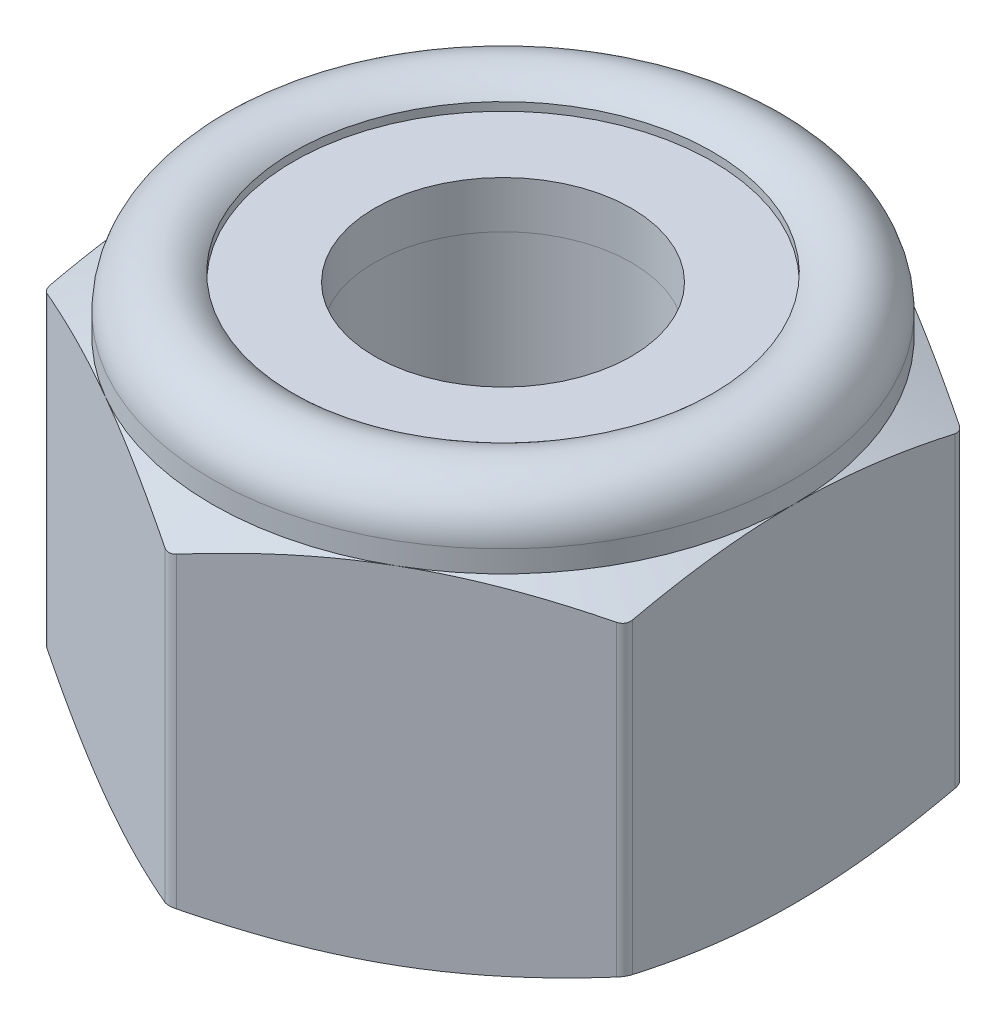
SolidWorks part; units mm, degrees
material "Alloy Steel"
ref_plane "Front Plane" through (0, 0, 0) normal (0, 0, 1) x (1, 0, 0)
ref_plane "Top Plane" through (0, 0, 0) normal (0, 1, 0) x (1, 0, 0)
ref_plane "Right Plane" through (0, 0, 0) normal (1, 0, 0) x (0, 0, -1)
sketch "Sketch1" plane through (0, 0, 0) normal (0, 0, 1) x (1, 0, 0)
  line L0 (0, -2.5) -> (0, 2.5) construction
  line L1 (3.5, 0) -> (-3.5, 0) construction
  line L2 (2, -2.5) -> (-2, -2.5) construction
  line L3 (2, -2.5) -> (2, -1.8) construction
  point P4 (0, 0)
  point P8 (0, 0)
  point P11 (0, -2.5)
  dimension "Height" = 5
  dimension "Width" = 7
  dimension "Thread Size" = 4
  dimension "Thread Pitch" = 0.7
sketch "Sketch2" plane through (0, 0, 0) normal (0, 1, 0) x (1, 0, 0)
  line L0 (-2, 0.3063) -> (-2, -0.3063) construction
  line L1 (0, 4.0415) -> (-3.5, 2.0207)
  line L2 (-3.5, 2.0207) -> (-3.5, -2.0207)
  line L3 (-3.5, -2.0207) -> (0, -4.0415)
  line L4 (0, -4.0415) -> (3.5, -2.0207)
  line L5 (3.5, -2.0207) -> (3.5, 2.0207)
  line L6 (3.5, 2.0207) -> (0, 4.0415)
  line L7 (-2, -0.3063) -> (-1.5453, -0.0438) construction
  line L8 (-1.5453, -0.0438) -> (-1.5453, 0.0437) construction
  line L9 (-1.5453, 0.0437) -> (-2, 0.3063) construction
  line L10 (-1.5453, 0) -> (-2, 0) construction
  line L11 (-1.7727, 0.175) -> (-1.7727, -0.175) construction
  line L12 (2, 0) -> (-2, 0) construction
  line L13 (3.5, 0) -> (-3.5, 0) construction
  circle A0 centre (0, 0) radius 3.5 construction
  circle A1 centre (0, 0) radius 1.5453
  point P19 (0, -1.5453)
  dimension "D1" = 0.0875
  dimension "D2" = 0.35
  dimension "D3" = 60
extrude "Boss-Extrude1" add sketch "Sketch2" along normal up to vertex (2.5 mm away) and the other way up to vertex (2.5 mm away) up to point (0, 2.5, 0) other way up to point (0, -2.5, 0)
fillet "Fillet1" radius 0.14 6 edges at (-3.5, 0, -2.0207) (0, 0, -4.0415) (-3.5, 0, 2.0207) (3.5, 0, -2.0207) (3.5, 0, 2.0207) (0, 0, 4.0415)
sketch "Sketch3" plane through (0, 0, 0) normal (1, 0, 0) x (0, 0, -1)
  line L0 (4.0415, 1.6667) -> (4.0415, 3.5)
  line L2 (3.5, -2.5) -> (4.0415, -2.2475)
  line L3 (2.0611, -2.5) -> (4.001, -2.5) construction
  line L4 (4.0415, 2.5) -> (4.0415, -2.5) construction
  line L5 (4.0415, -2.2475) -> (4.0415, -2.5)
  line L6 (4.0415, -2.5) -> (3.5, -2.5)
  line L7 (3.5, 1.6667) -> (4.0415, 1.4142)
  line L8 (4.0415, 1.4142) -> (4.0415, 1.6667)
  line L11 (3.5, 1.6667) -> (3.5, 1.9275)
  line L12 (2.0611, 2.5) -> (4.001, 2.5) construction
  line L13 (1.5453, 1.6667) -> (2.5227, 1.6667)
  line L14 (2.5227, 1.6667) -> (2.5227, 2.3323)
  line L15 (2.5227, 1.6667) -> (3.5, 1.6667) construction
  line L16 (2.5227, 2.3323) -> (2.9275, 1.9275) construction
  line L17 (2.9275, 1.9275) -> (2.9275, 2.5) construction
  line L18 (1.5453, 1.6667) -> (1.5453, 3.5)
  line L19 (1.5453, 3.5) -> (4.0415, 3.5)
  line L21 (1.5453, -2.5) -> (1.5453, -2.1)
  line L22 (-1.9399, -2.5) -> (1.9399, -2.5) construction
  line L24 (1.9453, -2.5) -> (1.5453, -2.5)
  line L25 (1.5453, -2.1) -> (1.9453, -2.5)
  arc A0 (3.5, 1.9275) -> (2.5227, 2.3323) centre (2.9275, 1.9275) ccw
  point P0 (3.5, 1.6667)
  point P1 (3.5, 0)
  point P14 (1.5453, 0)
  dimension "D1" = 4.1667
  dimension "D2" = 25
  dimension "D3" = 45
  dimension "D4" = 1
  dimension "D5" = 0.4
revolve "Cut-Revolve2" cut sketch "Sketch3" angle 360 about L0
sketch "Sketch4" plane through (0, 0, 0) normal (1, 0, 0) x (0, 0, -1)
  line L0 (-2.5227, 2.3323) -> (-2.5227, 1.6667) construction
  line L1 (-1.5453, 1.6667) -> (-2.5227, 1.6667)
  line L2 (-1.5453, 1.6667) -> (-1.5453, 2.2323)
  line L3 (-1.5453, 2.2323) -> (-2.5227, 2.2323)
  line L4 (-2.5227, 1.6667) -> (-2.5227, 2.2323)
  line L5 (2.5227, 2.3323) -> (-2.5227, 2.3323) construction
  line L6 (1.5453, 1.6667) -> (-1.5453, 1.6667) construction
  dimension "D1" = 0.1
revolve "Revolve1" add sketch "Sketch4" angle 360 about L0
sketch "Sketch5" plane through (0, 0, 0) normal (0, 1, 0) x (1, 0, 0)
  circle A0 centre (0, 0) radius 1.5453 construction
  point P0 (0, -1.5453)
sketch "Sketch6" [suppressed] plane through (0, 0, 0) normal (0, 0, 1) x (1, 0, 0)
  line L0 (2, 1.6667) -> (2, -2.5)
  line L2 (0, -2.5) -> (3.5, -2.5) construction
  line L3 (2, -2.5) -> (0, -2.5)
  line L4 (0, -2.5) -> (0, 1.6667)
  line L5 (0, -2.5) -> (0, 2.5) construction
  line L6 (0, 1.6667) -> (2, 1.6667)
  line L7 (3.5, 1.6667) -> (1.75, 1.6667) construction
revolve "Revolve2" [suppressed] add sketch "Sketch6" angle 360 about L4
sketch "Sketch7" [suppressed] plane through (0, -2.5, 0) normal (0, -1, 0) x (1, 0, 0)
  circle A2 centre (0, 0) radius 2
  circle A3 centre (0, 0) radius 2
  dimension "D1" = 0
curve "Helix/Spiral1" [suppressed] pitch 0.7 height 5 turns 7.1429
sketch "Sketch8" [suppressed] plane through (0, 0, 0) normal (0, 0, 1) x (1, 0, 0)
  line L0 (2.0758, -2.4563) -> (1.4696, -2.8063) construction
  line L1 (1.4696, -2.8063) -> (2.0758, -3.1563) construction
  line L2 (2.0758, -3.1563) -> (2.0758, -2.4563) construction
  line L3 (1.5453, -2.7625) -> (1.5453, -2.85)
  line L4 (2, -2.5) -> (2, -3.1125) construction
  line L5 (2, -2.8063) -> (2.0758, -2.8063) construction
  line L6 (1.4696, -2.8063) -> (1.5453, -2.8063) construction
  line L7 (2.0379, -2.8063) -> (2.0379, -3.1344) construction
  line L8 (1.5453, -2.7625) -> (2.0758, -2.4563)
  line L9 (2.0758, -2.4563) -> (2.0379, -3.1344)
  line L10 (1.5453, -2.85) -> (2.0379, -3.1344)
  dimension "D1" = 0.7
  dimension "D2" = 0.0875
sweep "Cut-Sweep1" [suppressed] cut profiles "Sketch8" path "Helix/Spiral1"
sketch "Sketch9" [suppressed] plane through (0, 0, 0) normal (0, 0, 1) x (1, 0, 0)
  line L0 (0, -0.5) -> (0, -2.5)
  line L1 (0, -0.5) -> (0, -0.1)
  line L2 (0, -2.5) -> (2, -2.5)
  line L3 (2, -2.5) -> (2.4, -2.5)
  line L4 (2.4, -2.5) -> (0, -0.1)
  dimension "D1" = 0.4
revolve "Revolve3" [suppressed] add sketch "Sketch9" angle 360 about L0
sketch "Sketch10" [suppressed] plane through (0, -2.5, 0) normal (0, -1, 0) x (1, 0, 0)
  circle A0 centre (0, 0) radius 1.9453 construction
  circle A1 centre (0, 0) radius 1.9453
extrude "Boss-Extrude2" [suppressed] add sketch "Sketch10" against normal up to surface (4.1667 mm away)
combine bodies "Combine1" [suppressed] operation type add bodies to combine 110 109
equation "\"D1@Sketch3\"=\"Height@sketch1\"*(5/6)"
equation "\"D5@Sketch3\"=\"Thread Size@Sketch1\"*.1"
equation "\"D4@Helix/Spiral1\"=\"Thread Pitch@sketch1\""
equation "\"D3@Helix/Spiral1\"=\"Height@sketch1\""
equation "\"D1@Sketch8\"=\"Thread Pitch@sketch1\""
equation "\"D2@Sketch8\"=\"Thread Pitch@sketch1\"/8"
equation "\"D1@Sketch9\"=\"Thread Size@Sketch1\" * .1"
equation "\"D1@Sketch2\"=\"Thread Pitch@sketch1\"/8"
equation "\"D2@Sketch2\"=\"Thread Pitch@sketch1\"/2"
equation "\"D1@Sketch4\" = \"Height@Sketch1\" * .02"
equation "\"D1@Fillet1\"=\"Width@sketch1\"*.02"
